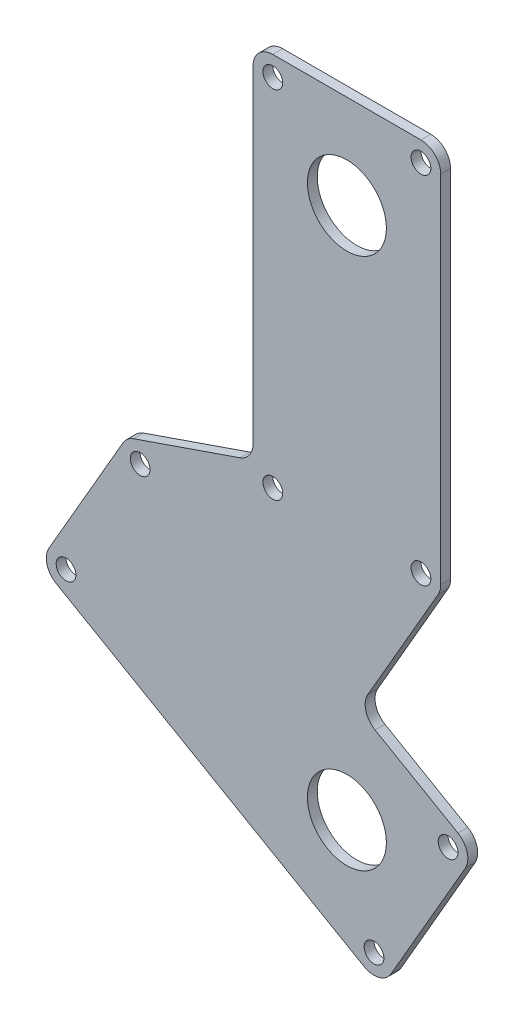
SolidWorks part; units mm, degrees
ref_plane "Front Plane" through (0, 0, 0) normal (0, 0, 1) x (1, 0, 0)
ref_plane "Top Plane" through (0, 0, 0) normal (0, 1, 0) x (1, 0, 0)
ref_plane "Right Plane" through (0, 0, 0) normal (1, 0, 0) x (0, 0, -1)
sketch "Sketch1" plane through (0, 0, 0) normal (0, 0, 1) x (1, 0, 0)
  line L0 (0, 18) -> (0, -97.2542) construction
  line L1 (-20.9317, -22.6319) -> (-20.0657, -23.1319)
  line L2 (-7.5, -18) -> (7.5, -18) construction
  line L3 (-7.5, -18) -> (-7.5, 18) construction
  line L4 (-7.5, 18) -> (7.5, 18) construction
  line L5 (7.5, -18) -> (7.5, 18) construction
  line L6 (-7.5, -18) -> (7.5, 18) construction
  line L7 (-7.5, 18) -> (7.5, -18) construction
  line L8 (-7.5, -18) -> (7.5, -18) construction
  line L9 (-7.5, -18) -> (-7.5, -27.5) construction
  line L10 (-7.5, -27.5) -> (7.5, -27.5) construction
  line L11 (7.5, -18) -> (7.5, -27.5) construction
  line L12 (10.2452, -40.6319) -> (2.7452, -53.6223) construction
  line L13 (2.7452, -53.6223) -> (-28.4317, -35.6223) construction
  line L14 (-28.4317, -35.6223) -> (-20.9317, -22.6319) construction
  line L15 (-24.6817, -29.1271) -> (63.5538, -80.0699) construction
  line L16 (-7.5, -18) -> (-20.9317, -22.6319) construction
  line L17 (7.5, -18) -> (-1.6136, -33.7853) construction
  line L18 (-1.6136, -33.7853) -> (10.2452, -40.6319) construction
  line L19 (-9.5, -16.5741) -> (-22.2902, -20.9848)
  line L20 (-9.5, -16.5741) -> (-9.5, 20)
  line L21 (-9.5, 20) -> (9.5, 20)
  line L22 (9.5, -18.5359) -> (9.5, 20)
  line L23 (9.5, -18.5359) -> (1.1184, -33.0532)
  line L24 (1.1184, -33.0532) -> (12.9772, -39.8999)
  line L25 (12.9772, -39.8999) -> (3.4772, -56.3544)
  line L26 (3.4772, -56.3544) -> (-31.1638, -36.3544)
  line L27 (-31.1638, -36.3544) -> (-22.2902, -20.9848)
  line L28 (10.2452, -40.6319) -> (18.4724, -45.3819) construction
  line L29 (18.4724, -45.3819) -> (10.9724, -58.3723) construction
  line L30 (10.9724, -58.3723) -> (2.7452, -53.6223) construction
  line L31 (0, 10.5) -> (0, -43.3771)
  circle A0 centre (-7.5, 18) radius 1
  circle A1 centre (7.5, 18) radius 1
  circle A2 centre (7.5, -18) radius 1
  circle A3 centre (-7.5, -18) radius 1
  circle A4 centre (-20.9317, -22.6319) radius 1
  circle A5 centre (10.2452, -40.6319) radius 1
  circle A6 centre (-28.4317, -35.6223) radius 1
  circle A7 centre (2.7452, -53.6223) radius 1
  circle A8 centre (0, -43.3771) radius 4
  circle A9 centre (0, 10.5) radius 4
  point P3 (0, 0)
  point P22 (0, -43.3771)
  point P23 (0, 10.5)
  dimension "D3" = 2
  dimension "D6" = 120
  dimension "D9" = 2
  dimension "D10" = 8
  dimension "D11" = 8
  dimension "D1" = 15
  dimension "D2" = 36
  dimension "D4" = 9.5
  dimension "D5" = 2.5
  dimension "D7" = 7.5
  dimension "D8" = 7.5
  dimension "D12" = 53.8771
extrude "Boss-Extrude1" add sketch "Sketch1" along normal blind 1 contours L27 L26 L25 L24 L23 L22 L21 L20 L19 A9 A8 A7 A6 A5 A4 A3 A2 A1 A0 region at (-4.8338, -19.8722, 0)
fillet "Fillet1" radius 2 9 edges at (-9.5, 20, 0.5) (9.5, 20, 0.5) (9.5, -18.5359, 0.5) (-22.2902, -20.9848, 0.5) (-31.1638, -36.3544, 0.5) (3.4772, -56.3544, 0.5) (12.9772, -39.8999, 0.5) (1.1184, -33.0532, 0.5) (-9.5, -16.5741, 0.5)
ref_axis "Axis1" through (0, 10.5, 1) along (0, 0, -1)
ref_axis "Axis2" through (0, -43.3771, 1) along (0, 0, -1)
ref_plane "Plane1" through (0, 0, 0) normal (1, 0, 0) x (0, 0, -1)
